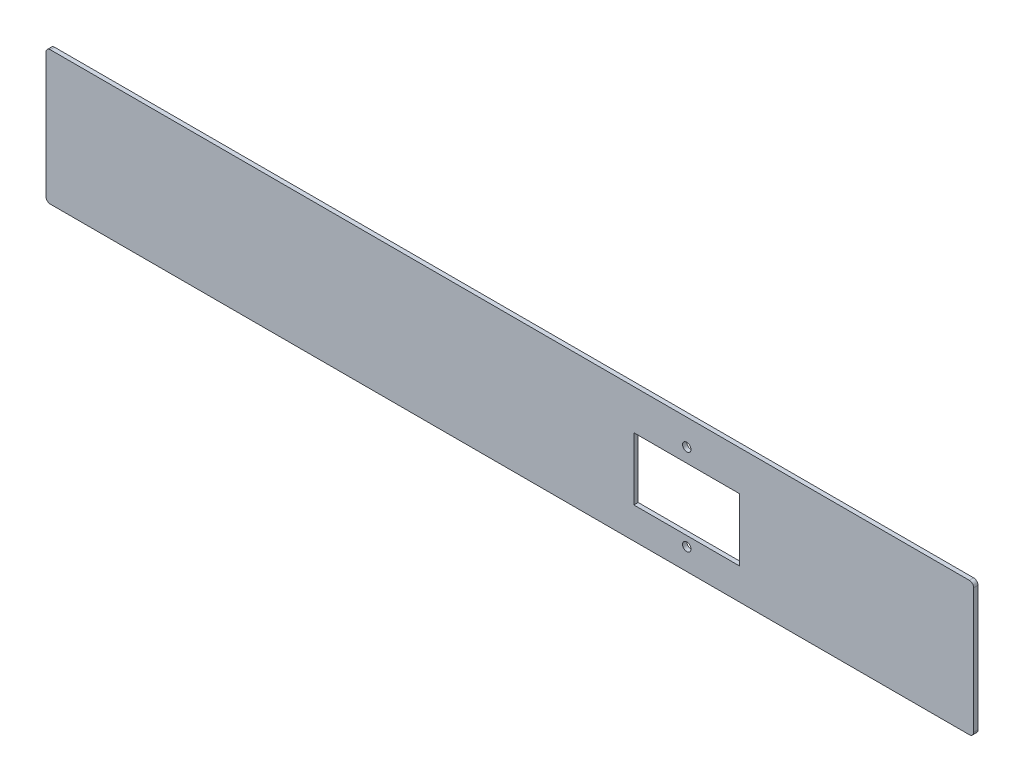
SolidWorks part; units mm, degrees
ref_plane "Front Plane" through (0, 0, 0) normal (0, 0, 1) x (1, 0, 0)
ref_plane "Top Plane" through (0, 0, 0) normal (0, 1, 0) x (1, 0, 0)
ref_plane "Right Plane" through (0, 0, 0) normal (1, 0, 0) x (0, 0, -1)
sketch "Sketch1" plane through (0, 0, 0) normal (0, 0, 1) x (1, 0, 0)
  line L1 (-351.9248, 29.7035) -> (78.0752, 29.7035)
  line L2 (-351.9248, 29.7035) -> (-351.9248, -32.2965)
  line L3 (-351.9248, -32.2965) -> (78.0752, -32.2965)
  line L4 (78.0752, 29.7035) -> (78.0752, -32.2965)
  line L5 (-79.4248, 11.2035) -> (-30.4248, 11.2035)
  line L6 (-79.4248, 11.2035) -> (-79.4248, -17.7965)
  line L7 (-79.4248, -17.7965) -> (-30.4248, -17.7965)
  line L8 (-30.4248, 11.2035) -> (-30.4248, -17.7965)
  circle A0 centre (-54.9248, 17.7035) radius 1.95
  circle A1 centre (-54.9248, -22.2965) radius 1.95
  point P12 (-54.9248, 11.2035)
  dimension "D3" = 133
  dimension "D4" = 40
  dimension "D1" = 430
  dimension "D2" = 62
  dimension "D5" = 10
  dimension "D6" = 49
  dimension "D7" = 29
  dimension "D8" = 6.5
extrude "Boss-Extrude1" add sketch "Sketch1" along normal blind 2
fillet "Fillet1" radius 2 4 edges at (78.0752, 29.7035, 1) (78.0752, -32.2965, 1) (-351.9248, -32.2965, 1) (-351.9248, 29.7035, 1)
